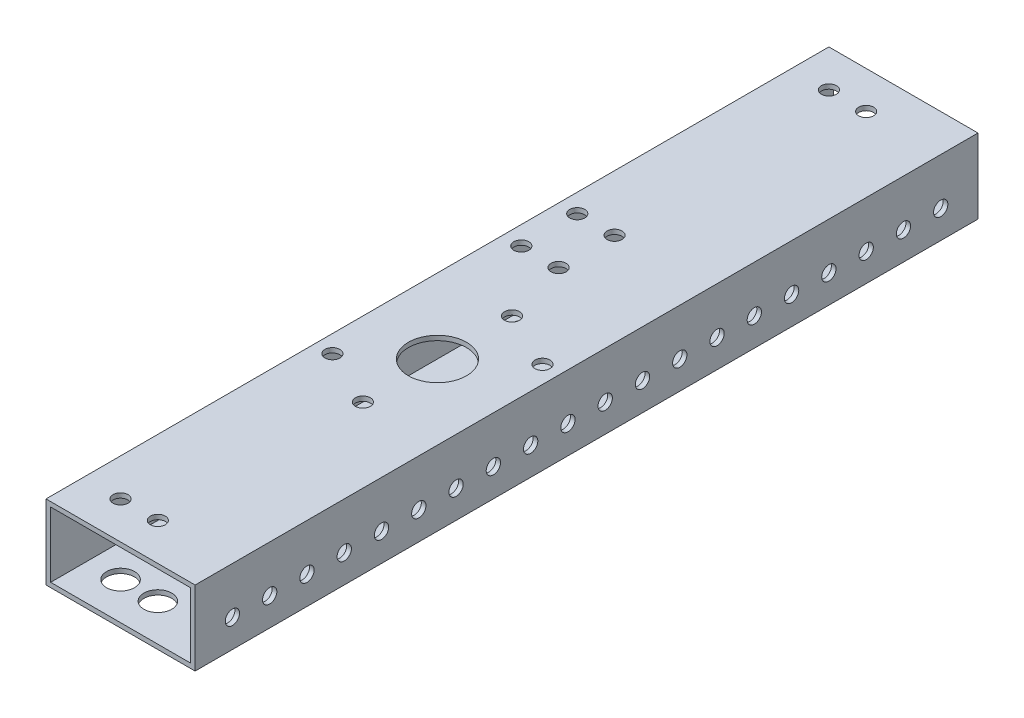
SolidWorks part; units mm, degrees
other "Markup1"
sketch "Sketch7" plane through (25.4, 12.7, -127) normal (0.9965, 0.0171, -0.0817) x (-0.082, 0.0128, -0.9966)
sketch "Sketch8" plane through (25.4, 12.7, -127) normal (0.9965, 0.0171, -0.0817) x (-0.082, 0.0128, -0.9966)
sketch "Sketch9" plane through (25.4, 12.7, -127) normal (0.9965, 0.0171, -0.0817) x (-0.082, 0.0128, -0.9966)
sketch "Sketch12" plane through (25.4, 12.7, -127) normal (0.9965, 0.0171, -0.0817) x (-0.082, 0.0128, -0.9966)
sketch "Sketch13" plane through (25.4, 12.7, -127) normal (0.9965, 0.0171, -0.0817) x (-0.082, 0.0128, -0.9966)
sketch "Sketch14" plane through (25.4, 12.7, -127) normal (0.9965, 0.0171, -0.0817) x (-0.082, 0.0128, -0.9966)
sketch "Sketch15" plane through (25.4, 12.7, -133.35) normal (0.9965, 0.0171, -0.0817) x (-0.082, 0.0128, -0.9966)
sketch "Sketch16" plane through (25.4, 12.7, -133.35) normal (0.9965, 0.0171, -0.0817) x (-0.082, 0.0128, -0.9966)
material "6061-T6 (SS)"
ref_plane "Front Plane" through (0, 0, 0) normal (0, 0, 1) x (1, 0, 0)
ref_plane "Top Plane" through (0, 0, 0) normal (0, 1, 0) x (1, 0, 0)
ref_plane "Right Plane" through (0, 0, 0) normal (1, 0, 0) x (0, 0, -1)
sketch "Sketch1" plane through (0, 0, 0) normal (0, 0, 1) x (1, 0, 0)
  line L0 (-23.8125, 11.1125) -> (23.8125, 11.1125)
  line L1 (-25.4, -12.7) -> (25.4, -12.7)
  line L2 (-25.4, -12.7) -> (-25.4, 12.7)
  line L3 (-25.4, 12.7) -> (25.4, 12.7)
  line L4 (25.4, -12.7) -> (25.4, 12.7)
  line L5 (-25.4, -12.7) -> (25.4, 12.7) construction
  line L6 (-25.4, 12.7) -> (25.4, -12.7) construction
  line L7 (23.8125, -11.1125) -> (23.8125, 11.1125)
  line L8 (-23.8125, -11.1125) -> (23.8125, -11.1125)
  line L9 (-23.8125, -11.1125) -> (-23.8125, 11.1125)
  point P0 (0, 0)
  dimension "D1" = 50.8
  dimension "D2" = 25.4
  dimension "D3" = 1.5875
extrude "Boss-Extrude1" add sketch "Sketch1" along normal mid plane 266.7
sketch "Sketch3" plane through (0, 12.7, 0) normal (0, 1, 0) x (1, 0, 0)
  line L0 (25.4, 133.35) -> (-25.4, 133.35) construction
  line L1 (25.4, -133.35) -> (-25.4, -133.35) construction
  line L3 (-25.4, -133.35) -> (-25.4, 133.35) construction
  line L4 (25.4, -133.35) -> (25.4, 133.35) construction
  circle A0 centre (-12.7, -120.65) radius 2.5527
  circle A1 centre (0, -120.65) radius 2.5527
  circle A2 centre (-12.7, 120.65) radius 2.5527
  circle A3 centre (0, 120.65) radius 2.5527
  dimension "D5" = 5.1054
  dimension "D1" = 12.7
  dimension "D2" = 12.7
  dimension "D3" = 12.7
  dimension "D4" = 12.7
  dimension "D6" = 12.7
  dimension "D7" = 12.7
  dimension "D8" = 12.7
  dimension "D9" = 25.4
  dimension "D10" = 12.7
  dimension "D11" = 25.4
extrude "Cut-Extrude1" cut sketch "Sketch3" against normal up to surface (1.5875 mm away) up to face at (0, 11.1125, 0)
sketch "Sketch5" plane through (0, -12.7, 0) normal (0, -1, 0) x (1, 0, 0)
  circle A0 centre (-12.7, -120.65) radius 2.5527 construction
  circle A1 centre (0, -120.65) radius 2.5527 construction
  circle A2 centre (0, 120.65) radius 2.5527 construction
  circle A3 centre (-12.7, 120.65) radius 2.5527 construction
  circle A4 centre (-12.7, -120.65) radius 2.5527
  circle A5 centre (0, -120.65) radius 2.5527
  circle A6 centre (0, 120.65) radius 2.5527
  circle A7 centre (-12.7, 120.65) radius 2.5527
  circle A8 centre (-12.7, 120.65) radius 4.7625
  circle A9 centre (0, 120.65) radius 4.7625
  circle A10 centre (0, -120.65) radius 4.7625
  circle A11 centre (-12.7, -120.65) radius 4.7625
  dimension "D1" = 9.525
extrude "Cut-Extrude2" cut sketch "Sketch5" against normal up to surface (1.5875 mm away) contours A10 A5 | A5 | A11 A4 | A4 | A6 | A9 A6 | A8 A7 | A7 region at (-12.7, -12.7, -120.65) region at (0, -12.7, -120.65) region at (0, -12.7, 120.65) region at (-12.7, -12.7, 120.65) region at (-17.3278, -12.7, 120.65) region at (-4.6278, -12.7, 120.65) region at (-4.6278, -12.7, -120.65) region at (-17.3278, -12.7, -120.65) up to face at (0, -11.1125, 0)
sketch "Sketch6" plane through (25.4, 0, 0) normal (1, 0, 0) x (0, 0, -1)
  line L0 (-133.35, -12.7) -> (-133.35, 12.7) construction
  line L1 (-133.35, -12.7) -> (133.35, -12.7) construction
  line L2 (0, 12.7) -> (0, -12.7) construction
  line L3 (-133.35, 12.7) -> (133.35, 12.7) construction
  circle A0 centre (-120.65, -3.175) radius 2.4384
  circle A19 centre (-107.95, -3.175) radius 2.4384
  circle A20 centre (-95.25, -3.175) radius 2.4384
  circle A21 centre (-82.55, -3.175) radius 2.4384
  circle A22 centre (-69.85, -3.175) radius 2.4384
  circle A23 centre (-57.15, -3.175) radius 2.4384
  circle A24 centre (-44.45, -3.175) radius 2.4384
  circle A25 centre (-31.75, -3.175) radius 2.4384
  circle A26 centre (-19.05, -3.175) radius 2.4384
  circle A27 centre (-6.35, -3.175) radius 2.4384
  circle A28 centre (6.35, -3.175) radius 2.4384
  circle A29 centre (19.05, -3.175) radius 2.4384
  circle A30 centre (31.75, -3.175) radius 2.4384
  circle A31 centre (44.45, -3.175) radius 2.4384
  circle A32 centre (57.15, -3.175) radius 2.4384
  circle A33 centre (69.85, -3.175) radius 2.4384
  circle A34 centre (82.55, -3.175) radius 2.4384
  circle A35 centre (95.25, -3.175) radius 2.4384
  circle A36 centre (107.95, -3.175) radius 2.4384
  circle A37 centre (120.65, -3.175) radius 2.4384
  dimension "D1" = 4.8768
  dimension "D5" = 12.7
  dimension "D2" = 12.7
  dimension "D3" = 9.525
  dimension "D4" = 20
extrude "Cut-Extrude3" cut sketch "Sketch6" against normal up to next contours A0 | A19 | A20 | A21 | A23 | A22 | A24 | A25 | A26 | A27 | A28 | A29 | A30 | A31 | A32 | A37 | A36 | A35 | A34 | A33 | A24 | A33 region at (25.4, -3.175, 120.65) region at (25.4, -3.175, 107.95) region at (25.4, -3.175, 95.25) region at (25.4, -3.175, 82.55) region at (25.4, -3.175, 69.85) region at (25.4, -3.175, 57.15) region at (25.4, -3.175, 44.45) region at (25.4, -3.175, 31.75) region at (25.4, -3.175, 19.05) region at (25.4, -3.175, 6.35) region at (25.4, -3.175, -6.35) region at (25.4, -3.175, -19.05) region at (25.4, -3.175, -31.75) region at (25.4, -3.175, -44.45) region at (25.4, -3.175, -57.15) region at (25.4, -3.175, -69.85) region at (25.4, -3.175, -82.55) region at (25.4, -3.175, -95.25) region at (25.4, -3.175, -107.95) region at (25.4, -3.175, -120.65)
sketch "Sketch11" plane through (0, 12.7, 0) normal (0, 1, 0) x (1, 0, 0)
  line L0 (-25.4, -133.35) -> (-25.4, 133.35) construction
  line L1 (-6.35, 41.275) -> (-6.35, 22.225) construction
  line L2 (0, 0) -> (0, -50.8) construction
  line L3 (25.4, 133.35) -> (-25.4, 133.35) construction
  line L5 (-19.05, 41.275) -> (-3.7973, 41.275) construction
  line L6 (-19.05, 41.275) -> (-19.05, 22.225) construction
  line L7 (-19.05, 22.225) -> (-3.7973, 22.225) construction
  line L9 (-19.05, 41.275) -> (-16.8611, 39.9616) construction
  line L10 (-19.05, 22.225) -> (-16.8611, 23.5384) construction
  line L13 (-19.05, -34.925) -> (-19.05, -15.875) construction
  line L14 (-19.4575, -41.7268) -> (19.4575, -9.0732) construction
  line L15 (25.4, -133.35) -> (25.4, 133.35) construction
  circle A0 centre (0, -25.4) radius 9.906
  circle A1 centre (0, 0) radius 2.5527
  circle A2 centre (0, -50.8) radius 2.5527
  circle A4 centre (-19.05, 22.225) radius 2.5527
  circle A5 centre (-19.05, 41.275) radius 2.5527
  circle A7 centre (-6.35, 22.225) radius 2.5527
  circle A8 centre (-6.35, 41.275) radius 2.5527
  circle A13 centre (19.4575, -9.0732) radius 2.5527
  circle A14 centre (-19.4575, -41.7268) radius 2.5527
  point P2 (0, -25.4)
  point P8 (-3.175, 31.75)
  point P24 (0, -25.4)
  dimension "D1" = 19.812
  dimension "D3" = 5.1054
  dimension "D4" = 25.4
  dimension "D5" = 19.05
  dimension "D6" = 5.1054
  dimension "D7" = 12.7
  dimension "D10" = 50
  dimension "D13" = 5.9425
  dimension "D2" = 25.4
  dimension "D8" = 101.6
  dimension "D9" = 6.35
  dimension "D11" = 19.05
  dimension "D12" = 22.225
  dimension "1" = 25.4
extrude "Cut-Extrude4" cut sketch "Sketch11" against normal through all
